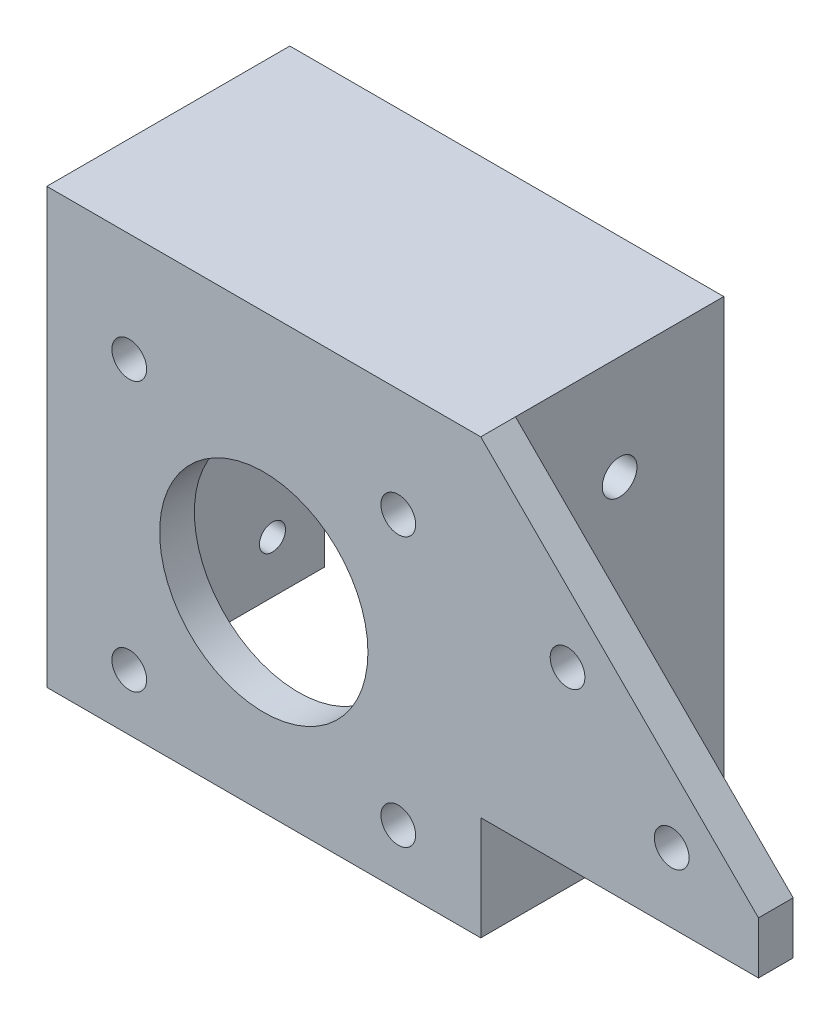
SolidWorks part; units mm, degrees
ref_plane "Front Plane" through (0, 0, 0) normal (0, 0, 1) x (1, 0, 0)
ref_plane "Top Plane" through (0, 0, 0) normal (0, 1, 0) x (1, 0, 0)
ref_plane "Right Plane" through (0, 0, 0) normal (1, 0, 0) x (0, 0, -1)
sketch "Sketch1" plane through (0, 0, 0) normal (0, 0, 1) x (1, 0, 0)
  line L0 (-50.3416, 0) -> (46.1674, 0) construction
  line L1 (0, -28.4394) -> (0, 79.8206) construction
  line L2 (57, 18) -> (25, 50)
  line L4 (-25, 0) -> (-25, 50)
  line L5 (-25, 50) -> (25, 50)
  line L6 (57, 12) -> (57, 18)
  line L7 (25, -2.2452) -> (25, 66.7313) construction
  line L10 (57, 12) -> (25, 12)
  line L11 (25, 12) -> (25, 0)
  line L12 (25, 0) -> (-25, 0)
  dimension "D1" = 50
  dimension "D2" = 38
  dimension "D3" = 6
  dimension "D5" = 25
  dimension "D6" = 45
  dimension "D7" = 50
extrude "Boss-Extrude1" add sketch "Sketch1" along normal blind 4
sketch "Sketch2" plane through (0, 0, 4) normal (0, 0, 1) x (1, 0, 0)
  line L0 (-39.1184, 22) -> (53, 22) construction
  line L1 (0, -8.7046) -> (0, 47.1631) construction
  line L2 (57, 18) -> (25, 50) construction
  line L3 (-15.5, 6.5) -> (15.5, 6.5) construction
  line L4 (-15.5, 6.5) -> (-15.5, 37.5) construction
  line L5 (-15.5, 37.5) -> (15.5, 37.5) construction
  line L6 (15.5, 6.5) -> (15.5, 37.5) construction
  line L7 (-15.5, 6.5) -> (15.5, 37.5) construction
  line L8 (-15.5, 37.5) -> (15.5, 6.5) construction
  line L9 (-25, 0) -> (25, 0) construction
  circle A0 centre (0, 22) radius 12
  circle A1 centre (15.5, 6.5) radius 2
  circle A2 centre (15.5, 37.5) radius 2
  circle A3 centre (-15.5, 37.5) radius 2
  circle A4 centre (-15.5, 6.5) radius 2
  point P4 (0, 22)
  dimension "D1" = 4
  dimension "D4" = 24
  dimension "D2" = 31
  dimension "D3" = 22
extrude "Cut-Extrude1" cut sketch "Sketch2" against normal through all
sketch "Sketch9" plane through (0, 0, 0) normal (0, 0, -1) x (-1, 0, 0)
  line L0 (-61, 20) -> (-35, 20) construction
  line L1 (-35, 20) -> (-35, 48.0747) construction
  line L2 (-25, -5.4794) -> (-25, 53.2688) construction
  line L3 (-25, 12) -> (-57, 12) construction
  circle A1 centre (-47, 20) radius 2
  circle A2 centre (-35, 32) radius 2
  dimension "D2" = 10
  dimension "D5" = 4
  dimension "D1" = 12
  dimension "D3" = 12
  dimension "D4" = 8
extrude "Cut-Extrude2" cut sketch "Sketch9" against normal blind 4
sketch "Sketch13" plane through (0, 0, 4) normal (0, 0, 1) x (1, 0, 0)
  line L8 (-25, 34.0255) -> (-45, 34.0255)
  line L9 (-25, 50) -> (-25, 0) construction
  line L10 (-45, 34.0255) -> (-45, 96.6007)
  line L11 (-45, 96.6007) -> (-32.0913, 96.6007)
  line L13 (57, 18) -> (25, 50) construction
  line L14 (25, 50) -> (19, 56)
  line L15 (-25, 34.0255) -> (-25, 50)
  line L17 (-32.0913, 96.6007) -> (-32.0913, 74.4017)
  line L20 (19, 56) -> (-3.8448, 56)
  line L21 (25, 50) -> (-25, 50)
  arc A3 (-3.8448, 56) -> (-32.0913, 74.4017) centre (-11.974, 74.4017) cw
  dimension "D1" = 20
  dimension "D2" = 6
extrude "Boss-Extrude7" [suppressed] add sketch "Sketch13" against normal blind 4
sketch "Sketch16" [suppressed] plane through (0, 0, 4) normal (0, 0, 1) x (1, 0, 0)
  line L0 (-38.5457, 92.6569) -> (2.0281, 52.0832) construction
  line L1 (-45, 34.0255) -> (-25, 34.0255) construction
  line L2 (-38.5457, 96.6007) -> (-38.5457, 85.5222) construction
  line L3 (-32.0913, 96.6007) -> (-45, 96.6007) construction
  circle A0 centre (2.0281, 52.0832) radius 2
  circle A1 centre (-38.5457, 92.6569) radius 2
  dimension "D3" = 4
  dimension "D1" = 57.38
  dimension "D2" = 45
extrude "Cut-Extrude6" [suppressed] cut sketch "Sketch16" against normal blind 4
sketch "Sketch17" plane through (0, 0, 0) normal (0, 0, -1) x (-1, 0, 0)
  line L0 (-25, 0) -> (-25, 50)
  line L2 (-25, 50) -> (25, 50)
  line L3 (25, 50) -> (25, 0) construction
  line L4 (25, 50) -> (25, 0)
  line L5 (25, 0) -> (21, 0)
  line L6 (25, 0) -> (-25, 0) construction
  line L7 (21, 0) -> (21, 46)
  line L8 (21, 46) -> (-21, 46)
  line L9 (-21, 46) -> (-21, 0)
  line L10 (-21, 0) -> (-25, 0)
  dimension "D1" = 42
  dimension "D2" = 21
  dimension "D3" = 4
extrude "Boss-Extrude8" add sketch "Sketch17" along normal blind 24
sketch "Sketch18" plane through (25, 0, 0) normal (1, 0, 0) x (0, 0, -1)
  line L0 (12, 4.8734) -> (12, 63.3892) construction
  circle A0 centre (12, 38) radius 2
  circle A1 centre (12, 20) radius 2
  dimension "D1" = 4
  dimension "D2" = 20
  dimension "D3" = 18
  dimension "D4" = 12
extrude "Cut-Extrude7" cut sketch "Sketch18" against normal up to surface (4 mm away) up to face at (21, 23, -12)
sketch "Sketch19" plane through (-25, 0, 0) normal (-1, 0, 0) x (0, 0, 1)
  line L2 (4, 0) -> (-24, 0) construction
  line L4 (-18, 6) -> (-4, 6) construction
  line L5 (-18, 6) -> (-18, 41) construction
  line L6 (-18, 41) -> (-4, 41) construction
  line L7 (-4, 6) -> (-4, 41) construction
  circle A0 centre (-18, 6) radius 1.5
  circle A2 centre (-18, 41) radius 1.5
  circle A3 centre (-4, 6) radius 1.5
  circle A4 centre (-4, 41) radius 1.5
  dimension "D5" = 3
  dimension "D1" = 6
  dimension "D2" = 6
  dimension "D3" = 35
  dimension "D4" = 14
extrude "Cut-Extrude8" cut sketch "Sketch19" against normal blind 10
equation "\"motor_plate_thickness\"=4"
equation "\"D1@Boss-Extrude1\"=\"motor_plate_thickness\""
equation "\"motor_hub_diameter\"=24"
equation "\"D4@Sketch2\"=\"motor_hub_diameter\""
equation "\"motor_mount_hole_od\"=4"
equation "\"D1@Sketch2\"=\"motor_mount_hole_od\""
equation "\"motor_mount_hole_spacing\"=31"
equation "\"D2@Sketch2\"=\"motor_mount_hole_spacing\""
